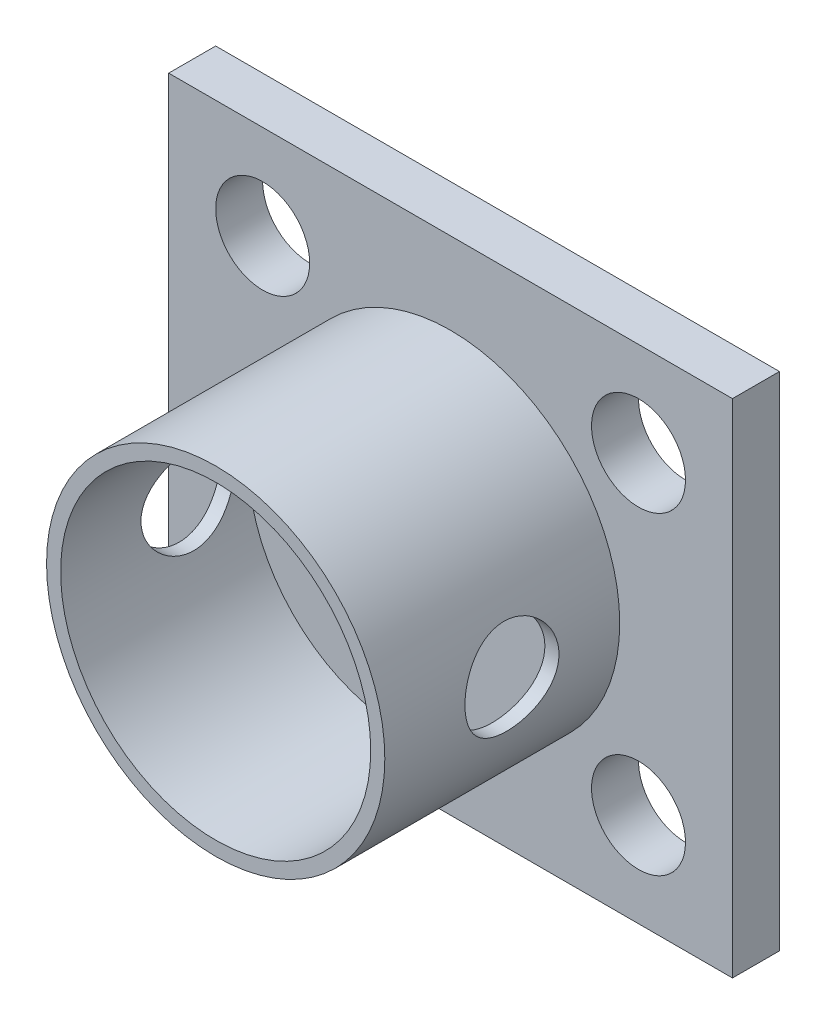
SolidWorks part; units mm, degrees
ref_plane "Front Plane" through (0, 0, 0) normal (0, 0, 1) x (1, 0, 0)
ref_plane "Top Plane" through (0, 0, 0) normal (0, 1, 0) x (1, 0, 0)
ref_plane "Right Plane" through (0, 0, 0) normal (1, 0, 0) x (0, 0, -1)
sketch "Sketch1" plane through (0, 0, 0) normal (0, 0, 1) x (1, 0, 0)
  line L1 (-30, 26.7) -> (30, 26.7)
  line L2 (-30, 26.7) -> (-30, -26.7)
  line L3 (-30, -26.7) -> (30, -26.7)
  line L4 (30, 26.7) -> (30, -26.7)
  circle A0 centre (0, 0) radius 16.5
  circle A1 centre (0, 0) radius 18
  circle A2 centre (-20, 16.7) radius 5
  circle A3 centre (20, 16.7) radius 5
  circle A4 centre (20, -16.7) radius 5
  circle A5 centre (-20, -16.7) radius 5
  circle A6 centre (-7.5, 0) radius 2.5
  circle A7 centre (7.5, 0) radius 2.5
  point P8 (30, 0)
  point P9 (0, 26.7)
  point P20 (0, 0)
  point P21 (0, 0)
  dimension "D1" = 33
  dimension "D2" = 36
  dimension "D5" = 10
  dimension "D6" = 10
  dimension "D7" = 10
  dimension "D8" = 10
  dimension "D10" = 5
  dimension "D11" = 5
  dimension "D3" = 60
  dimension "D4" = 53.4
  dimension "D9" = 10
  dimension "D12" = 15
  dimension "D13" = 7.5
extrude "Boss-Extrude1" add sketch "Sketch1" along normal blind 5 contours L4 L1 L2 L3 A5 A4 A3 A2 A1 region at (0, 25.8968, 0)
extrude "Boss-Extrude2" add sketch "Sketch1<3>" along normal blind 30 contours A1 A0 region at (-17.4909, 0, 0)
sketch "Sketch1<3>" plane through (0, 0, 0) normal (0, 0, 1) x (1, 0, 0) same geometry as "Sketch1"
extrude "Boss-Extrude3" add sketch "Sketch1<4>" along normal blind 10 contours A0 A7 A6 region at (0, 0, 0)
sketch "Sketch1<4>" plane through (0, 0, 0) normal (0, 0, 1) x (1, 0, 0) same geometry as "Sketch1"
sketch "Sketch2" plane through (0, 0, 0) normal (1, 0, 0) x (0, 0, -1)
  circle A2 centre (-16.4605, 0.4827) radius 5
  point P1 (0, 0)
  point P3 (0, 0)
  dimension "D1" = 10
extrude "Cut-Extrude1" cut sketch "Sketch2" against normal through all and the other way through all
